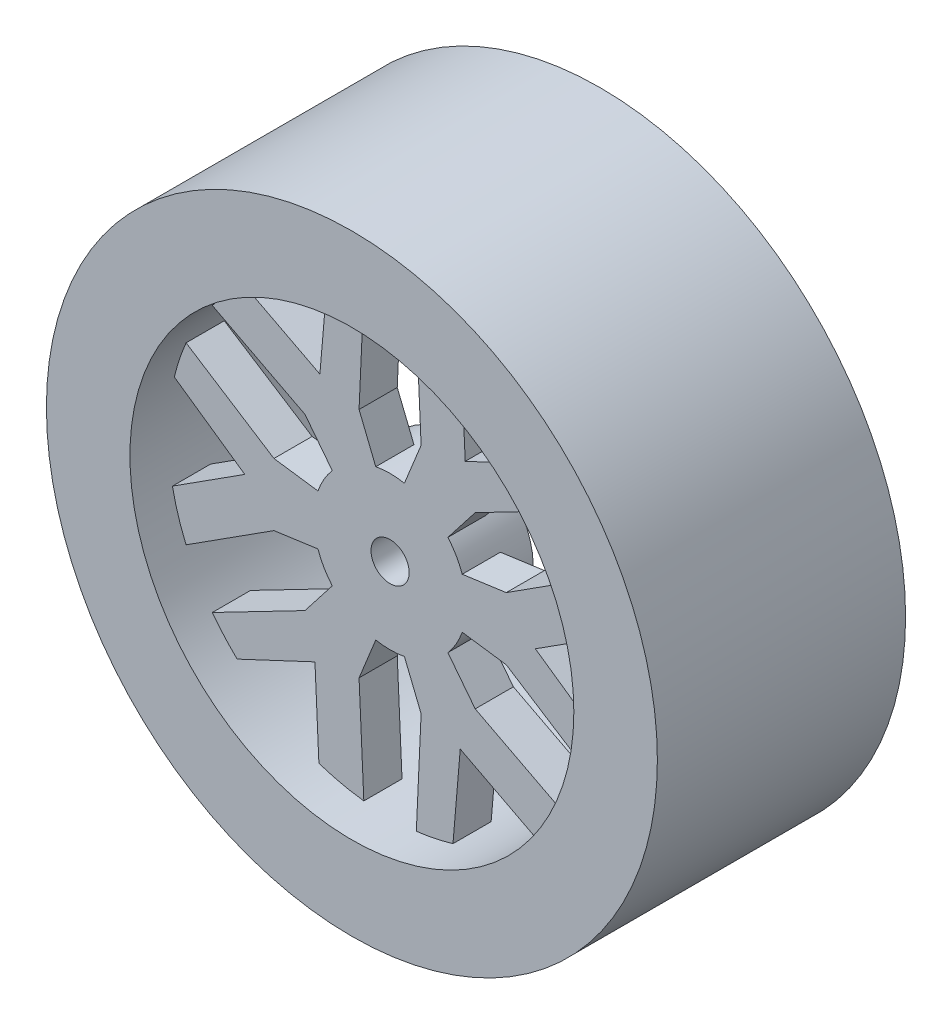
SolidWorks part; units mm, degrees
ref_plane "Plan de face" through (0, 0, 0) normal (0, 0, 1) x (1, 0, 0)
ref_plane "Plan de dessus" through (0, 0, 0) normal (0, 1, 0) x (1, 0, 0)
ref_plane "Plan de droite" through (0, 0, 0) normal (1, 0, 0) x (0, 0, -1)
sketch "Esquisse1" plane through (0, 0, 0) normal (0, 0, 1) x (1, 0, 0)
  circle A0 centre (0, 0) radius 32
  dimension "D1" = 64
extrude "Boss.-Extru.1" add sketch "Esquisse1" along normal blind 26
sketch "Esquisse3" plane through (0, 0, 26) normal (0, 0, 1) x (1, 0, 0)
  circle A0 centre (0, 0) radius 23.25
  dimension "D1" = 46.5
extrude "Enlèv. mat.-Extru.2" cut sketch "Esquisse3" against normal blind 4
sketch "Esquisse4" plane through (0, 0, 0) normal (0, 0, -1) x (-1, 0, 0)
  circle A0 centre (0, 0) radius 23.25
  dimension "D1" = 46.5
extrude "Enlèv. mat.-Extru.3" cut sketch "Esquisse4" against normal blind 18
ref_axis "Axe1" through (0, 0, 27.3) along (0, 0, -1)
sketch "Esquisse6" plane through (0, 0, 18) normal (0, 0, -1) x (-1, 0, 0)
  circle A0 centre (0, 0) radius 8
  dimension "D1" = 16
extrude "Boss.-Extru.5" add sketch "Esquisse6" along normal blind 3
sketch "Esquisse2" plane through (0, 0, 26) normal (0, 0, 1) x (1, 0, 0)
  circle A0 centre (0, 0) radius 2
  dimension "D1" = 4
extrude "Enlèv. mat.-Extru.4" cut sketch "Esquisse2" against normal through all
sketch "Esquisse7" plane through (0, 0, 15) normal (0, 0, -1) x (-1, 0, 0)
  line L0 (-3.4641, 6) -> (3.4641, 6)
  line L1 (3.4641, 6) -> (6.9282, 0)
  line L2 (6.9282, 0) -> (3.4641, -6)
  line L3 (3.4641, -6) -> (-3.4641, -6)
  line L4 (-3.4641, -6) -> (-6.9282, 0)
  line L5 (-6.9282, 0) -> (-3.4641, 6)
  point P3 (0, 6)
  dimension "D1" = 12
  dimension "D2" = 12
  dimension "D3" = 12
extrude "Enlèv. mat.-Extru.5" cut sketch "Esquisse7" against normal up to surface (3 mm away) up to face at (-23.25, 0, 18)
sketch "Esquisse8" plane through (0, 0, 22) normal (0, 0, 1) x (1, 0, 0)
  line L0 (-3.25, 12.1718) -> (-1.5, 7.8581)
  line L2 (1.5, 7.8581) -> (3.25, 12.1718)
  line L3 (3.25, 12.1718) -> (2.75, 23.0868)
  line L5 (-2.75, 23.0868) -> (-3.25, 12.1718)
  circle A0 centre (0, 0) radius 23.25 construction
  circle A1 centre (0, 0) radius 23.25 construction
  arc A4 (-2.75, 23.0868) -> (2.75, 23.0868) centre (0, 0) cw
  arc A5 (1.5, 7.8581) -> (-1.5, 7.8581) centre (0, 0) ccw
  dimension "D4" = 8
  dimension "D1" = 5.5
  dimension "D2" = 3
  dimension "D3" = 6.5
extrude "Enlèv. mat.-Extru.8" cut sketch "Esquisse8" against normal through all
pattern_circular "Répétition circulaire1" count 6 over 360 about axis through (0, 0, 27.3) along (0, 0, -1) of "Enlèv. mat.-Extru.8" reverse direction yes
sketch "Esquisse9" plane through (0, 0, 22) normal (0, 0, 1) x (1, 0, 0)
  line L0 (7.869, 13.0311) -> (7.4571, 22.0217)
  line L1 (7.869, 13.0311) -> (16.0174, 16.8524)
  line L2 (3.25, 12.1718) -> (2.75, 23.0868) construction
  arc A0 (16.0174, 16.8524) -> (7.4571, 22.0217) centre (0, 0) ccw
  circle A1 centre (0, 0) radius 23.25 construction
  dimension "D1" = 9
  dimension "D2" = 10
extrude "Enlèv. mat.-Extru.9" cut sketch "Esquisse9" against normal through all
pattern_circular "Répétition circulaire2" count 6 every 60 about axis through (0, 0, 27.3) along (0, 0, -1) of "Enlèv. mat.-Extru.9"
